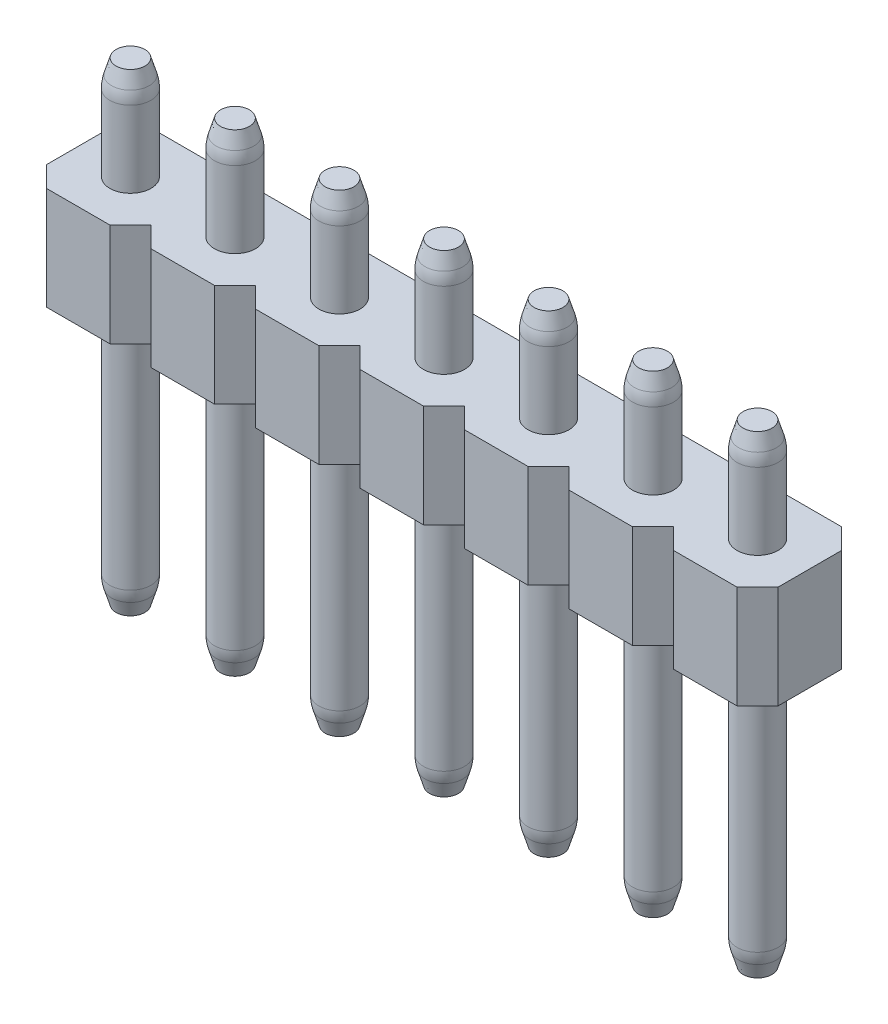
SolidWorks part; units mm, degrees
material "Brass"
ref_plane "Front Plane" through (0, 0, 0) normal (0, 0, 1) x (1, 0, 0)
ref_plane "Top Plane" through (0, 0, 0) normal (0, 1, 0) x (1, 0, 0)
ref_plane "Right Plane" through (0, 0, 0) normal (1, 0, 0) x (0, 0, -1)
sketch "Sketch1" plane through (0, 0, 0) normal (0, 1, 0) x (1, 0, 0)
  line L0 (0, 0) -> (2.54, 0) construction
  circle A0 centre (0, 0) radius 0.5
  circle A1 centre (2.54, 0) radius 0.5
  circle A2 centre (5.08, 0) radius 0.5
  circle A3 centre (7.62, 0) radius 0.5
  circle A4 centre (10.16, 0) radius 0.5
  circle A5 centre (12.7, 0) radius 0.5
  circle A6 centre (15.24, 0) radius 0.5
  circle A7 centre (17.78, 0) radius 0.5
  circle A8 centre (20.32, 0) radius 0.5
  circle A9 centre (22.86, 0) radius 0.5
  circle A10 centre (25.4, 0) radius 0.5
  circle A11 centre (27.94, 0) radius 0.5
  circle A12 centre (30.48, 0) radius 0.5
  circle A13 centre (33.02, 0) radius 0.5
  circle A14 centre (35.56, 0) radius 0.5
  circle A15 centre (38.1, 0) radius 0.5
  dimension "D1" = 1
  dimension "D3" = 2.54
  dimension "D2" = 16
extrude "Boss-Extrude1" add sketch "Sketch1" along normal blind 11.5
ref_plane "Plane1" through (0, 6.5, 0) normal (0, 1, 0) x (1, 0, 0)
sketch "Sketch2" plane through (0, 6.5, 0) normal (0, 1, 0) x (1, 0, 0)
  line L0 (-1.27, 0.77) -> (-0.77, 1.27)
  line L1 (-0.77, -1.27) -> (0.77, -1.27)
  line L2 (-1.27, -0.77) -> (-1.27, 0.77)
  line L3 (-0.77, 1.27) -> (0.77, 1.27)
  line L5 (-1.27, -1.27) -> (1.27, 1.27) construction
  line L6 (-1.27, 1.27) -> (1.27, -1.27) construction
  line L7 (0.77, 1.27) -> (1.27, 0.77)
  line L8 (0.77, -1.27) -> (1.27, -0.77)
  line L9 (-1.27, -0.77) -> (-0.77, -1.27)
  line L10 (1.27, 0.77) -> (1.77, 1.27)
  line L11 (1.77, 1.27) -> (3.31, 1.27)
  line L12 (3.31, 1.27) -> (3.81, 0.77)
  line L14 (3.31, -1.27) -> (3.81, -0.77)
  line L15 (1.77, -1.27) -> (3.31, -1.27)
  line L16 (1.27, -0.77) -> (1.77, -1.27)
  line L17 (3.81, 0.77) -> (4.31, 1.27)
  line L18 (4.31, 1.27) -> (5.85, 1.27)
  line L19 (5.85, 1.27) -> (6.35, 0.77)
  line L20 (6.35, -0.77) -> (6.35, 0.77) construction
  line L21 (5.85, -1.27) -> (6.35, -0.77)
  line L22 (4.31, -1.27) -> (5.85, -1.27)
  line L23 (3.81, -0.77) -> (4.31, -1.27)
  line L24 (6.35, 0.77) -> (6.85, 1.27)
  line L25 (6.85, 1.27) -> (8.39, 1.27)
  line L26 (8.39, 1.27) -> (8.89, 0.77)
  line L27 (8.89, -0.77) -> (8.89, 0.77) construction
  line L28 (8.39, -1.27) -> (8.89, -0.77)
  line L29 (6.85, -1.27) -> (8.39, -1.27)
  line L30 (6.35, -0.77) -> (6.85, -1.27)
  line L31 (8.89, 0.77) -> (9.39, 1.27)
  line L32 (9.39, 1.27) -> (10.93, 1.27)
  line L33 (10.93, 1.27) -> (11.43, 0.77)
  line L34 (11.43, -0.77) -> (11.43, 0.77) construction
  line L35 (10.93, -1.27) -> (11.43, -0.77)
  line L36 (9.39, -1.27) -> (10.93, -1.27)
  line L37 (8.89, -0.77) -> (9.39, -1.27)
  line L38 (11.43, 0.77) -> (11.93, 1.27)
  line L39 (11.93, 1.27) -> (13.47, 1.27)
  line L40 (13.47, 1.27) -> (13.97, 0.77)
  line L41 (13.97, -0.77) -> (13.97, 0.77) construction
  line L42 (13.47, -1.27) -> (13.97, -0.77)
  line L43 (11.93, -1.27) -> (13.47, -1.27)
  line L44 (11.43, -0.77) -> (11.93, -1.27)
  line L45 (13.97, 0.77) -> (14.47, 1.27)
  line L46 (14.47, 1.27) -> (16.01, 1.27)
  line L47 (16.01, 1.27) -> (16.51, 0.77)
  line L48 (16.51, -0.77) -> (16.51, 0.77) construction
  line L49 (16.01, -1.27) -> (16.51, -0.77)
  line L50 (14.47, -1.27) -> (16.01, -1.27)
  line L51 (13.97, -0.77) -> (14.47, -1.27)
  line L52 (16.51, 0.77) -> (17.01, 1.27)
  line L53 (17.01, 1.27) -> (18.55, 1.27)
  line L54 (18.55, 1.27) -> (19.05, 0.77)
  line L55 (19.05, -0.77) -> (19.05, 0.77) construction
  line L56 (18.55, -1.27) -> (19.05, -0.77)
  line L57 (17.01, -1.27) -> (18.55, -1.27)
  line L58 (16.51, -0.77) -> (17.01, -1.27)
  line L59 (19.05, 0.77) -> (19.55, 1.27)
  line L60 (19.55, 1.27) -> (21.09, 1.27)
  line L61 (21.09, 1.27) -> (21.59, 0.77)
  line L62 (21.59, -0.77) -> (21.59, 0.77) construction
  line L63 (21.09, -1.27) -> (21.59, -0.77)
  line L64 (19.55, -1.27) -> (21.09, -1.27)
  line L65 (19.05, -0.77) -> (19.55, -1.27)
  line L66 (21.59, 0.77) -> (22.09, 1.27)
  line L67 (22.09, 1.27) -> (23.63, 1.27)
  line L68 (23.63, 1.27) -> (24.13, 0.77)
  line L69 (24.13, -0.77) -> (24.13, 0.77) construction
  line L70 (23.63, -1.27) -> (24.13, -0.77)
  line L71 (22.09, -1.27) -> (23.63, -1.27)
  line L72 (21.59, -0.77) -> (22.09, -1.27)
  line L73 (24.13, 0.77) -> (24.63, 1.27)
  line L74 (24.63, 1.27) -> (26.17, 1.27)
  line L75 (26.17, 1.27) -> (26.67, 0.77)
  line L76 (26.67, -0.77) -> (26.67, 0.77) construction
  line L77 (26.17, -1.27) -> (26.67, -0.77)
  line L78 (24.63, -1.27) -> (26.17, -1.27)
  line L79 (24.13, -0.77) -> (24.63, -1.27)
  line L80 (26.67, 0.77) -> (27.17, 1.27)
  line L81 (27.17, 1.27) -> (28.71, 1.27)
  line L82 (28.71, 1.27) -> (29.21, 0.77)
  line L83 (29.21, -0.77) -> (29.21, 0.77) construction
  line L84 (28.71, -1.27) -> (29.21, -0.77)
  line L85 (27.17, -1.27) -> (28.71, -1.27)
  line L86 (26.67, -0.77) -> (27.17, -1.27)
  line L87 (29.21, 0.77) -> (29.71, 1.27)
  line L88 (29.71, 1.27) -> (31.25, 1.27)
  line L89 (31.25, 1.27) -> (31.75, 0.77)
  line L90 (31.75, -0.77) -> (31.75, 0.77) construction
  line L91 (31.25, -1.27) -> (31.75, -0.77)
  line L92 (29.71, -1.27) -> (31.25, -1.27)
  line L93 (29.21, -0.77) -> (29.71, -1.27)
  line L94 (31.75, 0.77) -> (32.25, 1.27)
  line L95 (32.25, 1.27) -> (33.79, 1.27)
  line L96 (33.79, 1.27) -> (34.29, 0.77)
  line L97 (34.29, -0.77) -> (34.29, 0.77) construction
  line L98 (33.79, -1.27) -> (34.29, -0.77)
  line L99 (32.25, -1.27) -> (33.79, -1.27)
  line L100 (31.75, -0.77) -> (32.25, -1.27)
  line L101 (34.29, 0.77) -> (34.79, 1.27)
  line L102 (34.79, 1.27) -> (36.33, 1.27)
  line L103 (36.33, 1.27) -> (36.83, 0.77)
  line L104 (36.83, -0.77) -> (36.83, 0.77) construction
  line L105 (36.33, -1.27) -> (36.83, -0.77)
  line L106 (34.79, -1.27) -> (36.33, -1.27)
  line L107 (34.29, -0.77) -> (34.79, -1.27)
  line L108 (36.83, 0.77) -> (37.33, 1.27)
  line L109 (37.33, 1.27) -> (38.87, 1.27)
  line L110 (38.87, 1.27) -> (39.37, 0.77)
  line L111 (39.37, -0.77) -> (39.37, 0.77)
  line L112 (38.87, -1.27) -> (39.37, -0.77)
  line L113 (37.33, -1.27) -> (38.87, -1.27)
  line L114 (36.83, -0.77) -> (37.33, -1.27)
  line L115 (-1.27, 0.77) -> (1.27, 0.77) construction
  point P0 (0, 0)
  dimension "D1" = 2.54
  dimension "D2" = 2.54
  dimension "D4" = 2.54
  dimension "D3" = 16
extrude "Boss-Extrude2" add sketch "Sketch2" along normal blind 2.5
chamfer "Chamfer1" distance 0.5 distance2 0.15 16 edges at (15.24, 11.5, 0.5) (12.7, 11.5, 0.5) (10.16, 11.5, 0.5) (7.62, 11.5, 0.5) (5.08, 11.5, 0.5) (2.54, 11.5, 0.5) (0, 11.5, 0.5) (38.1, 11.5, 0.5) (35.56, 11.5, 0.5) (33.02, 11.5, 0.5) (30.48, 11.5, 0.5) (27.94, 11.5, 0.5) (25.4, 11.5, 0.5) (22.86, 11.5, 0.5) (20.32, 11.5, 0.5) (17.78, 11.5, 0.5) first distance on face at (15.24, 11.5, 0.5) first distance on face at (12.7, 11.5, 0.5) first distance on face at (10.16, 11.5, 0.5) first distance on face at (7.62, 11.5, 0.5) first distance on face at (5.08, 11.5, 0.5) first distance on face at (2.54, 11.5, 0.5) first distance on face at (0, 11.5, 0.5) first distance on face at (38.1, 11.5, 0.5) first distance on face at (35.56, 11.5, 0.5) first distance on face at (33.02, 11.5, 0.5) first distance on face at (30.48, 11.5, 0.5) first distance on face at (27.94, 11.5, 0.5) first distance on face at (25.4, 11.5, 0.5) first distance on face at (22.86, 11.5, 0.5) first distance on face at (20.32, 11.5, 0.5) first distance on face at (17.78, 11.5, 0.5)
fillet "Fillet1" radius 1 16 edges at (38.1, 11, 0.5) (35.56, 11, 0.5) (33.02, 11, 0.5) (30.48, 11, 0.5) (27.94, 11, 0.5) (25.4, 11, 0.5) (22.86, 11, 0.5) (20.32, 11, 0.5) (17.78, 11, 0.5) (15.24, 11, 0.5) (12.7, 11, 0.5) (10.16, 11, 0.5) (7.62, 11, 0.5) (5.08, 11, 0.5) (2.54, 11, 0.5) (0, 11, 0.5)
chamfer "Chamfer2" distance 0.15 distance2 0.5 16 edges at (10.16, 0, 0.5) (17.78, 0, 0.5) (22.86, 0, 0.5) (27.94, 0, 0.5) (30.48, 0, 0.5) (0, 0, 0.5) (2.54, 0, 0.5) (5.08, 0, 0.5) (7.62, 0, 0.5) (12.7, 0, 0.5) (15.24, 0, 0.5) (20.32, 0, 0.5) (25.4, 0, 0.5) (33.02, 0, 0.5) (35.56, 0, 0.5) (38.1, 0, 0.5) first distance on face at (10.16, 0, 0.5) first distance on face at (17.78, 0, 0.5) first distance on face at (22.86, 0, 0.5) first distance on face at (27.94, 0, 0.5) first distance on face at (30.48, 0, 0.5) first distance on face at (0, 0, 0.5) first distance on face at (2.54, 0, 0.5) first distance on face at (5.08, 0, 0.5) first distance on face at (7.62, 0, 0.5) first distance on face at (12.7, 0, 0.5) first distance on face at (15.24, 0, 0.5) first distance on face at (20.32, 0, 0.5) first distance on face at (25.4, 0, 0.5) first distance on face at (33.02, 0, 0.5) first distance on face at (35.56, 0, 0.5) first distance on face at (38.1, 0, 0.5)
fillet "Fillet2" radius 1 16 edges at (30.48, 0.5, 0.5) (33.02, 0.5, 0.5) (35.56, 0.5, 0.5) (38.1, 0.5, 0.5) (27.94, 0.5, 0.5) (25.4, 0.5, 0.5) (22.86, 0.5, 0.5) (20.32, 0.5, 0.5) (17.78, 0.5, 0.5) (15.24, 0.5, 0.5) (12.7, 0.5, 0.5) (10.16, 0.5, 0.5) (7.62, 0.5, 0.5) (5.08, 0.5, 0.5) (2.54, 0.5, 0.5) (0, 0.5, 0.5)
sketch "Sketch3" plane through (0, 0, 1.27) normal (0, 0, 1) x (1, 0, 0)
  line L1 (39.37, 9) -> (39.37, 6.5) construction
  line L2 (16.51, 9) -> (16.51, 6.5) construction
  line L3 (16.51, 11.5) -> (16.51, 0)
  line L4 (39.37, 11.5) -> (39.37, 0)
  line L5 (39.37, 0) -> (16.51, 0)
  line L6 (16.51, 11.5) -> (39.37, 11.5)
extrude "Cut-Extrude1" cut sketch "Sketch3" against normal through all both and the other way through all
